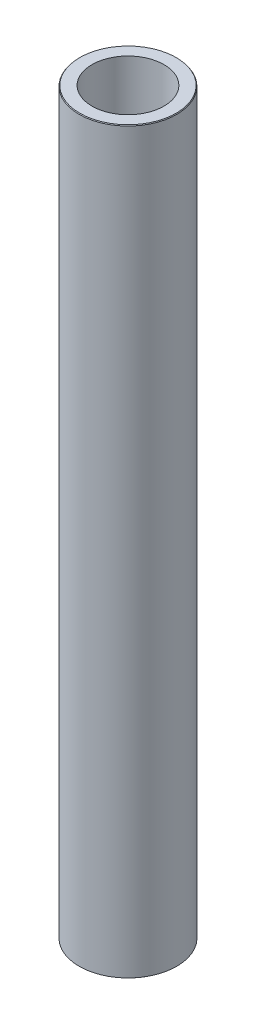
SolidWorks part; units mm, degrees
ref_plane "Front Plane" through (0, 0, 0) normal (0, 0, 1) x (1, 0, 0)
ref_plane "Top Plane" through (0, 0, 0) normal (0, 1, 0) x (1, 0, 0)
ref_plane "Right Plane" through (0, 0, 0) normal (1, 0, 0) x (0, 0, -1)
sketch "Sketch1" plane through (0, 0, 0) normal (0, 1, 0) x (1, 0, 0)
  circle A0 centre (0, 0) radius 27.5
  dimension "SHAFT_OD" = 55
extrude "Boss-Extrude1" add sketch "Sketch1" along normal blind 416.6263
sketch "Sketch2" plane through (0, 0, 0) normal (0, 1, 0) x (1, 0, 0)
  circle A0 centre (0, 0) radius 20.2937
  dimension "BORE_D" = 40.5874
extrude "Cut-Extrude1" cut sketch "Sketch2" along normal through all
chamfer "Chamfer1" distance 0.4339 angle 36.39 2 edges at (0, 416.6263, 27.5) (0, 0, 27.5) first distance on face at (0, 416.6263, 27.5) first distance on face at (0, 0, 20.2937)
